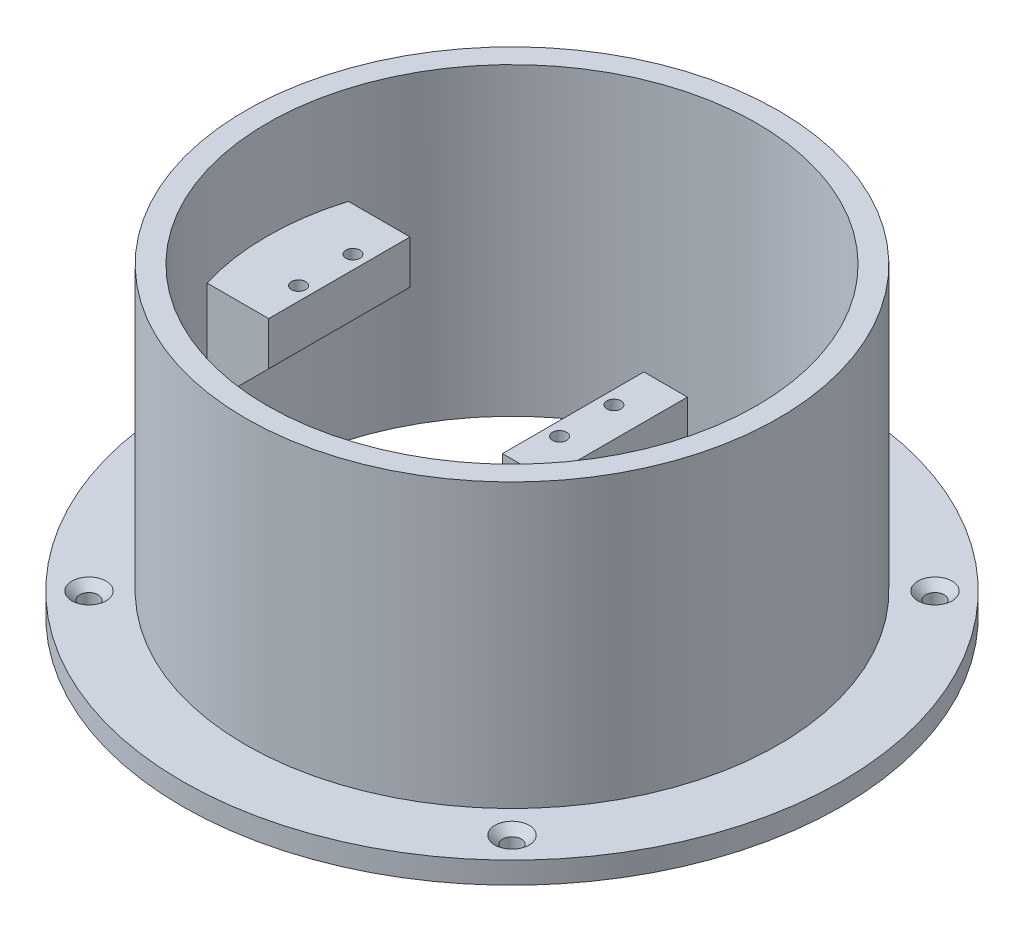
SolidWorks part; units mm, degrees
material "ABS"
ref_plane "Front Plane" through (0, 0, 0) normal (0, 0, 1) x (1, 0, 0)
ref_plane "Top Plane" through (0, 0, 0) normal (0, 1, 0) x (1, 0, 0)
ref_plane "Right Plane" through (0, 0, 0) normal (1, 0, 0) x (0, 0, -1)
sketch "Sketch1" plane through (0, 0, 0) normal (0, 1, 0) x (1, 0, 0)
  circle A0 centre (0, 0) radius 60.625
  circle A1 centre (0, 0) radius 45
  dimension "D1" = 121.25
  dimension "D2" = 90
extrude "Boss-Extrude1" add sketch "Sketch1" along normal blind 4
sketch "Sketch2" plane through (0, 4, 0) normal (0, 1, 0) x (1, 0, 0)
  circle A0 centre (0, 0) radius 45 construction
  circle A1 centre (0, 0) radius 45
  circle A2 centre (0, 0) radius 49
  dimension "D1" = 4
extrude "Boss-Extrude2" add sketch "Sketch2" along normal blind 52
ref_plane "Plane1" through (0, 36, 0) normal (0, 1, 0) x (1, 0, 0)
sketch "Sketch4" plane through (0, 0, 0) normal (0, 0, 1) x (1, 0, 0)
  line L0 (-60.625, 0) -> (60.625, 0) construction
  line L1 (11.25, 38) -> (19.25, 38)
  line L2 (11.25, 38) -> (11.25, 0)
  line L3 (11.25, 0) -> (19.25, 0)
  line L4 (19.25, 38) -> (19.25, 0)
  line L5 (49, 56) -> (-49, 56) construction
  line L6 (-45, 56) -> (-45, 4)
  line L7 (-31.75, 38) -> (-46.75, 38)
  line L8 (-31.75, 38) -> (-31.75, 30)
  line L9 (-31.75, 30) -> (-46.75, 30)
  line L10 (-46.75, 38) -> (-46.75, 30)
  line L11 (60.625, 4) -> (-60.625, 4) construction
  line L12 (-31.75, 30) -> (-45, 16.75)
  dimension "D1" = 11.25
  dimension "D2" = 8
  dimension "D3" = 18
  dimension "D4" = 43
  dimension "D5" = 15
  dimension "D6" = 8
  dimension "D7" = 45
  dimension "D8" = 18
extrude "Boss-Extrude4" add sketch "Sketch4" along normal mid plane 26 contours L9 L8 L7 L6 | L12 L9 L6 | L1 L4 L3 L2 region at (-38.375, 34, 0) region at (-40.5833, 25.5833, 0)
sketch "Sketch5" plane through (0, 0, 0) normal (0, -1, 0) x (1, 0, 0)
  line L0 (11.25, 13) -> (29.0674, 34.3524)
  line L1 (11.25, -13) -> (29.0674, -34.3524)
  line L2 (11.25, 13) -> (11.25, -13)
  circle A0 centre (0, 0) radius 45 construction
  arc A1 (29.0674, -34.3524) -> (29.0674, 34.3524) centre (0, 0) ccw
extrude "Boss-Extrude5" add sketch "Sketch5" against normal up to surface (4 mm away) contours L0 A1 L1 L2 up to face at (0, 4, 60.625)
sketch "Sketch7" plane through (0, 38, 0) normal (0, 1, 0) x (1, 0, 0)
  line L0 (-31.75, -13) -> (-31.75, 13) construction
  circle A0 centre (-34.25, 5) radius 1.3
  circle A1 centre (-34.25, -5) radius 1.3
  circle A2 centre (13.75, 5) radius 1.3
  circle A3 centre (13.75, -5) radius 1.3
  dimension "D1" = 2.6
  dimension "D2" = 2.6
  dimension "D3" = 10
  dimension "D4" = 5
  dimension "D5" = 2.5
  dimension "D7" = 48
  dimension "D6" = 2
extrude "Cut-Extrude4" cut sketch "Sketch7" against normal blind 7.2
sketch "Sketch9" plane through (11.25, 0, 0) normal (-1, 0, 0) x (0, 0, 1)
  line L0 (13, 0) -> (-13, 0) construction
  line L1 (-5, 29) -> (5, 29)
  line L2 (-5, 29) -> (-5, 0)
  line L3 (-5, 0) -> (5, 0)
  line L4 (5, 29) -> (5, 0)
  line L5 (-5, 29) -> (5, 0) construction
  line L6 (-5, 0) -> (5, 29) construction
  line L7 (0, 0) -> (0, 29) construction
  line L8 (13, 38) -> (-13, 38) construction
  line L10 (5, 5) -> (-5, 5)
  point P0 (0, 14.5)
  dimension "D1" = 10
  dimension "D2" = 9
  dimension "D3" = 5
extrude "Cut-Extrude7" cut sketch "Sketch9" against normal up to surface (8 mm away) contours L10 L4 L1 L2 region at (11.25, 17, 0) up to face at (19.25, 21, 0)
sketch "Sketch12" plane through (0, 4, 0) normal (0, 1, 0) x (1, 0, 0)
  line L5 (27.25, 19.6878) -> (27.25, -19.6878)
  line L6 (27.25, 19.6878) -> (27.25, -19.6878)
  line L9 (24.25, 16.0926) -> (24.25, -16.0926)
  line L10 (19.25, -13) -> (19.25, 13) construction
  line L18 (27.25, -19.6878) -> (29.4795, -22.3597)
  line L19 (29.4795, 22.3597) -> (27.25, 19.6878)
  line L21 (24.25, -16.0926) -> (29.4795, -22.3597)
  line L22 (29.4795, 22.3597) -> (24.25, 16.0926)
  arc A2 (29.4795, -22.3597) -> (29.4795, 22.3597) centre (0, 0) ccw
  arc A3 (29.4795, -22.3597) -> (29.4795, 22.3597) centre (0, 0) ccw
  dimension "D2" = 5
  dimension "D1" = 8
extrude "Cut-Extrude9" cut sketch "Sketch12" against normal through all contours L21 A3 L22 L6 | L6 L22 L9 L21 region at (31.3175, 4, 0) region at (25.8002, 4, 0)
sketch "Sketch14" plane through (0, 4, 0) normal (0, 1, 0) x (1, 0, 0)
  line L0 (0, 0) -> (-38.8909, 38.8909) construction
  line L1 (11.25, 13) -> (19.25, 13) construction
  circle A0 centre (-38.8909, 38.8909) radius 1.5
  circle A1 centre (38.8909, 38.8909) radius 1.5
  circle A2 centre (38.8909, -38.8909) radius 1.5
  circle A3 centre (-38.8909, -38.8909) radius 1.5
  point P15 (0, 0)
  dimension "D1" = 3
  dimension "D2" = 55
  dimension "D3" = 135
  dimension "D4" = 4
hole_wizard "CSK for M3 Countersunk Flat Head Screw1" positions "Sketch15" profile "Sketch17" countersink size "M3" standard "DIN" end condition up to next
sketch "Sketch15" plane through (0, 4, 0) normal (0, 1, 0) x (1, 0, 0)
  point P0 (-38.8909, 38.8909)
  point P3 (-38.8909, -38.8909)
  point P6 (38.8909, -38.8909)
  point P9 (38.8909, 38.8909)
sketch "Sketch17" plane through (-38.8909, 4, -38.8909) normal (1, 0, 0) x (0, 0, 1)
  line L0 (0, 0) -> (0, 4)
  line L1 (0, 4) -> (1.7, 4)
  line L2 (1.7, 4) -> (1.7, 1.45)
  line L3 (1.7, 1.45) -> (3.15, 0)
  line L5 (3.15, 0) -> (0, 0)
  line L6 (-1.7, 1.45) -> (-3.15, 0) construction
  line L11 (0, -6.35) -> (0, 107.95) construction
  dimension "Thru Hole Dia." = 3.4
  dimension "Thru Hole Depth" = 4
  dimension "Near C'Sink Dia." = 6.3
  dimension "Near C'Sink Angle" = 90
